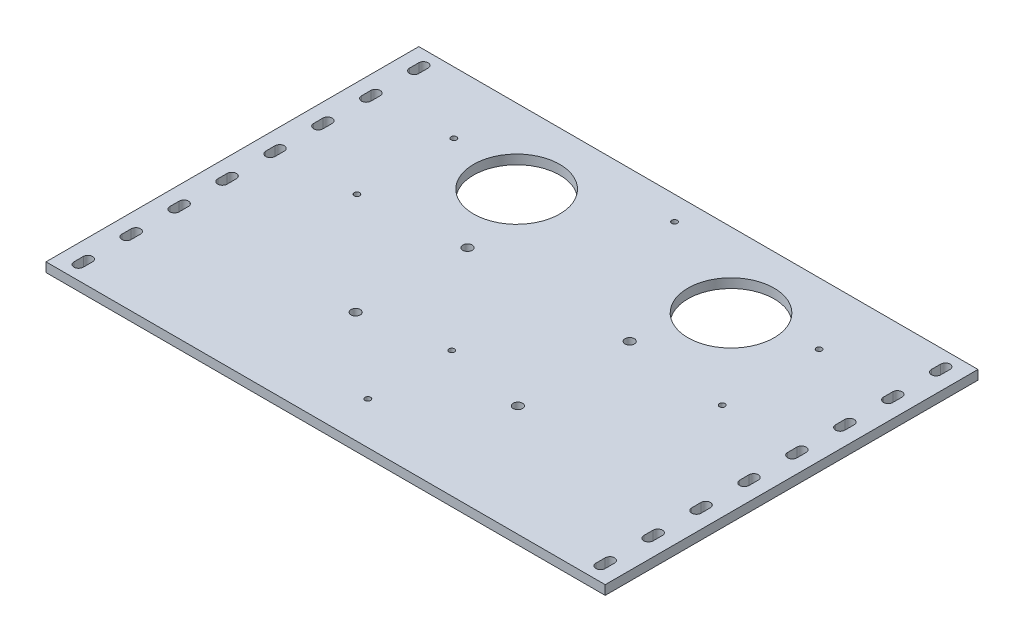
SolidWorks part; units mm, degrees
ref_plane "前基準面" through (0, 0, 0) normal (0, 0, 1) x (1, 0, 0)
ref_plane "上基準面" through (0, 0, 0) normal (0, 1, 0) x (1, 0, 0)
ref_plane "右基準面" through (0, 0, 0) normal (1, 0, 0) x (0, 0, -1)
sketch "草圖1" plane through (0, 0, 0) normal (0, 1, 0) x (1, 0, 0)
  line L0 (-130, 97.2315) -> (-150, 97.2315) construction
  line L1 (-150, 100) -> (150, 100)
  line L2 (-150, 100) -> (-150, -100)
  line L3 (-150, -100) -> (150, -100)
  line L4 (150, 100) -> (150, -100)
  line L5 (0, 100) -> (0, -100) construction
  line L6 (-150, 0) -> (150, 0) construction
  line L7 (-150, 100) -> (-130, 100) construction
  line L8 (150, -90) -> (-150, -90) construction
  line L9 (-150, 100) -> (-150, -100) construction
  line L10 (-150, -100) -> (-130, -100) construction
  line L11 (-130, 100) -> (-130, -100) construction
  line L12 (-142.25, 100) -> (-137.75, 100) construction
  line L13 (-142.25, 100) -> (-142.25, -100) construction
  line L14 (-142.25, -100) -> (-137.75, -100) construction
  line L15 (-137.75, 100) -> (-137.75, -100) construction
  line L16 (-140, 99.6012) -> (-140, 93.2772) construction
  line L17 (-140, 92.5) -> (-140, 87.5) construction
  line L18 (-137.5, 92.5) -> (-137.5, 87.5)
  line L19 (-142.5, 92.5) -> (-142.5, 87.5)
  line L20 (-140, 66.7857) -> (-140, 61.7857) construction
  line L21 (-137.5, 66.7857) -> (-137.5, 61.7857)
  line L22 (-142.5, 66.7857) -> (-142.5, 61.7857)
  line L23 (-140, 41.0714) -> (-140, 36.0714) construction
  line L24 (-137.5, 41.0714) -> (-137.5, 36.0714)
  line L25 (-142.5, 41.0714) -> (-142.5, 36.0714)
  line L26 (-140, 15.3571) -> (-140, 10.3571) construction
  line L27 (-137.5, 15.3571) -> (-137.5, 10.3571)
  line L28 (-142.5, 15.3571) -> (-142.5, 10.3571)
  line L29 (-140, -10.3571) -> (-140, -15.3571) construction
  line L30 (-137.5, -10.3571) -> (-137.5, -15.3571)
  line L31 (-142.5, -10.3571) -> (-142.5, -15.3571)
  line L32 (-140, -36.0714) -> (-140, -41.0714) construction
  line L33 (-137.5, -36.0714) -> (-137.5, -41.0714)
  line L34 (-142.5, -36.0714) -> (-142.5, -41.0714)
  line L35 (-140, -61.7857) -> (-140, -66.7857) construction
  line L36 (-137.5, -61.7857) -> (-137.5, -66.7857)
  line L37 (-142.5, -61.7857) -> (-142.5, -66.7857)
  line L38 (-140, -87.5) -> (-140, -92.5) construction
  line L39 (-137.5, -87.5) -> (-137.5, -92.5)
  line L40 (-142.5, -87.5) -> (-142.5, -92.5)
  line L41 (140, 92.5) -> (140, 87.5) construction
  line L44 (137.5, 92.5) -> (137.5, 87.5)
  line L47 (142.5, 92.5) -> (142.5, 87.5)
  line L50 (140, 66.7857) -> (140, 61.7857) construction
  line L53 (137.5, 66.7857) -> (137.5, 61.7857)
  line L56 (142.5, 66.7857) -> (142.5, 61.7857)
  line L59 (140, 41.0714) -> (140, 36.0714) construction
  line L62 (137.5, 41.0714) -> (137.5, 36.0714)
  line L65 (-150, -100) -> (150, -100) construction
  line L66 (-150, -100) -> (-150, -80) construction
  line L67 (-150, -80) -> (150, -80) construction
  line L68 (150, -100) -> (150, -80) construction
  line L69 (109.7962, -80) -> (109.7962, -100) construction
  line L76 (142.5, 41.0714) -> (142.5, 36.0714)
  line L77 (140, 15.3571) -> (140, 10.3571) construction
  line L78 (137.5, 15.3571) -> (137.5, 10.3571)
  line L79 (142.5, 15.3571) -> (142.5, 10.3571)
  line L80 (140, -10.3571) -> (140, -15.3571) construction
  line L81 (137.5, -10.3571) -> (137.5, -15.3571)
  line L82 (142.5, -10.3571) -> (142.5, -15.3571)
  line L83 (140, -36.0714) -> (140, -41.0714) construction
  line L84 (137.5, -36.0714) -> (137.5, -41.0714)
  line L85 (142.5, -36.0714) -> (142.5, -41.0714)
  line L86 (140, -61.7857) -> (140, -66.7857) construction
  line L87 (137.5, -61.7857) -> (137.5, -66.7857)
  line L88 (142.5, -61.7857) -> (142.5, -66.7857)
  line L89 (140, -87.5) -> (140, -92.5) construction
  line L90 (137.5, -87.5) -> (137.5, -92.5)
  line L91 (142.5, -87.5) -> (142.5, -92.5)
  line L92 (134.459, 100) -> (134.459, 80) construction
  line L93 (-150, 100) -> (150, 100) construction
  line L94 (-150, 100) -> (-150, 80) construction
  line L95 (-150, 80) -> (150, 80) construction
  line L96 (150, 100) -> (150, 80) construction
  arc A9 (-137.5, 92.5) -> (-142.5, 92.5) centre (-140, 92.5) ccw
  arc A10 (-142.5, 87.5) -> (-137.5, 87.5) centre (-140, 87.5) ccw
  arc A11 (-137.5, 66.7857) -> (-142.5, 66.7857) centre (-140, 66.7857) ccw
  arc A12 (-142.5, 61.7857) -> (-137.5, 61.7857) centre (-140, 61.7857) ccw
  arc A13 (-137.5, 41.0714) -> (-142.5, 41.0714) centre (-140, 41.0714) ccw
  arc A14 (-142.5, 36.0714) -> (-137.5, 36.0714) centre (-140, 36.0714) ccw
  arc A15 (-137.5, 15.3571) -> (-142.5, 15.3571) centre (-140, 15.3571) ccw
  arc A16 (-142.5, 10.3571) -> (-137.5, 10.3571) centre (-140, 10.3571) ccw
  arc A17 (-137.5, -10.3571) -> (-142.5, -10.3571) centre (-140, -10.3571) ccw
  arc A18 (-142.5, -15.3571) -> (-137.5, -15.3571) centre (-140, -15.3571) ccw
  arc A19 (-137.5, -36.0714) -> (-142.5, -36.0714) centre (-140, -36.0714) ccw
  arc A20 (-142.5, -41.0714) -> (-137.5, -41.0714) centre (-140, -41.0714) ccw
  arc A21 (-137.5, -61.7857) -> (-142.5, -61.7857) centre (-140, -61.7857) ccw
  arc A22 (-142.5, -66.7857) -> (-137.5, -66.7857) centre (-140, -66.7857) ccw
  arc A23 (-137.5, -87.5) -> (-142.5, -87.5) centre (-140, -87.5) ccw
  arc A24 (-142.5, -92.5) -> (-137.5, -92.5) centre (-140, -92.5) ccw
  arc A45 (137.5, 92.5) -> (142.5, 92.5) centre (140, 92.5) cw
  arc A46 (142.5, 87.5) -> (137.5, 87.5) centre (140, 87.5) cw
  arc A47 (137.5, 66.7857) -> (142.5, 66.7857) centre (140, 66.7857) cw
  arc A48 (142.5, 61.7857) -> (137.5, 61.7857) centre (140, 61.7857) cw
  arc A49 (137.5, 41.0714) -> (142.5, 41.0714) centre (140, 41.0714) cw
  arc A50 (142.5, 36.0714) -> (137.5, 36.0714) centre (140, 36.0714) cw
  arc A51 (137.5, 15.3571) -> (142.5, 15.3571) centre (140, 15.3571) cw
  arc A52 (142.5, 10.3571) -> (137.5, 10.3571) centre (140, 10.3571) cw
  arc A53 (137.5, -10.3571) -> (142.5, -10.3571) centre (140, -10.3571) cw
  arc A54 (142.5, -15.3571) -> (137.5, -15.3571) centre (140, -15.3571) cw
  arc A55 (137.5, -36.0714) -> (142.5, -36.0714) centre (140, -36.0714) cw
  arc A56 (142.5, -41.0714) -> (137.5, -41.0714) centre (140, -41.0714) cw
  arc A57 (137.5, -61.7857) -> (142.5, -61.7857) centre (140, -61.7857) cw
  arc A58 (142.5, -66.7857) -> (137.5, -66.7857) centre (140, -66.7857) cw
  arc A59 (137.5, -87.5) -> (142.5, -87.5) centre (140, -87.5) cw
  arc A60 (142.5, -92.5) -> (137.5, -92.5) centre (140, -92.5) cw
  point P6 (0, 0)
  point P17 (109.7962, -90)
  point P33 (-140, 97.2315)
  point P35 (-140, 90)
  point P42 (-137.5, 90)
  point P43 (-140, 64.2857)
  point P44 (0, 0)
  point P51 (-140, 38.5714)
  point P58 (-140, 12.8571)
  point P65 (-140, -12.8571)
  point P75 (-140, -38.5714)
  point P82 (-140, -64.2857)
  point P89 (-140, -90)
  point P99 (0, 0)
  point P107 (140, 90)
  point P114 (140, 64.2857)
  point P121 (140, 38.5714)
  point P128 (140, 12.8571)
  point P135 (140, -12.8571)
  point P142 (140, -38.5714)
  point P149 (140, -64.2857)
  point P163 (140, -90)
  dimension "D3" = 300
  dimension "D2" = 200
  dimension "D4" = 20
  dimension "D9" = 20
  dimension "D10" = 4.5
  dimension "D11" = 5
  dimension "D12" = 5
  dimension "D13" = 10
  dimension "D15" = 10
  dimension "D16" = 20
  dimension "D17" = 200
  dimension "D14" = 8
extrude "填料-伸長1" add sketch "草圖1" along normal blind 5
sketch "草圖2" plane through (0, 5, 0) normal (0, 1, 0) x (1, 0, 0)
  line L0 (0, 116.4556) -> (0, -113.9778) construction
  line L1 (90, 60) -> (25, 60) construction
  line L2 (-57.5, 92.5) -> (-57.5, 27.5) construction
  line L3 (-90, 60) -> (-25, 60) construction
  line L4 (57.5, 92.5) -> (57.5, 27.5) construction
  line L10 (7.5, -57.8553) -> (-7.5, -57.8553) construction
  line L15 (7.5, -57.8553) -> (7.5, 12.1447) construction
  line L16 (7.5, 12.1447) -> (-7.5, 12.1447) construction
  line L17 (-7.5, -57.8553) -> (-7.5, 12.1447) construction
  line L20 (-7.5, 12.1447) -> (7.5, 12.1447) construction
  line L30 (150, 100) -> (-150, 100) construction
  line L31 (-36, 29.6447) -> (36, 29.6447)
  line L32 (-36, 29.6447) -> (-36, -50.3553)
  line L33 (-36, -50.3553) -> (36, -50.3553)
  line L34 (36, 29.6447) -> (36, -50.3553)
  line L36 (36, -50.3553) -> (-36, -50.3553) construction
  line L37 (36, -50.3553) -> (36, 19.6447) construction
  line L38 (36, 19.6447) -> (-36, 19.6447) construction
  line L39 (-36, -50.3553) -> (-36, 19.6447) construction
  line L52 (144, 10.7857) -> (94, 10.7857)
  line L53 (-144, 70.7857) -> (-94, 70.7857)
  line L54 (-144, 70.7857) -> (-144, 10.7857)
  line L55 (-144, 10.7857) -> (-94, 10.7857)
  line L56 (-94, 70.7857) -> (-94, 10.7857)
  line L57 (94, 70.7857) -> (94, 10.7857)
  line L58 (144, 70.7857) -> (94, 70.7857)
  line L59 (144, 70.7857) -> (144, 10.7857)
  line L60 (-7.5, -10.3553) -> (7.5, -10.3553)
  line L61 (-7.5, -10.3553) -> (-7.5, -35.3553)
  line L62 (-7.5, -35.3553) -> (7.5, -35.3553)
  line L63 (7.5, -10.3553) -> (7.5, -35.3553)
  line L68 (-7.5, -19.8553) -> (7.5, -19.8553) construction
  line L69 (-7.5, -19.8553) -> (-7.5, -89.8553) construction
  line L70 (-7.5, -89.8553) -> (7.5, -89.8553) construction
  line L71 (7.5, -19.8553) -> (7.5, -89.8553) construction
  line L75 (240, -50.3553) -> (-240, -50.3553) construction
  line L76 (240, -50.3553) -> (240, 29.6447) construction
  line L77 (240, 29.6447) -> (-240, 29.6447) construction
  line L78 (-240, -50.3553) -> (-240, 29.6447) construction
  line L79 (35, 29.6447) -> (-35, 29.6447)
  line L80 (35, 29.6447) -> (35, -50.3553)
  line L81 (35, -50.3553) -> (-35, -50.3553)
  line L82 (-35, 29.6447) -> (-35, -50.3553)
  line L83 (0, -50.3553) -> (0, 29.6447) construction
  line L84 (35, -10.3553) -> (-35, -10.3553) construction
  circle A0 centre (-57.5, 60) radius 32.5
  circle A1 centre (-57.5, 60) radius 22.1
  circle A2 centre (-72, 60) radius 2
  circle A3 centre (-43, 60) radius 2
  circle A4 centre (43, 60) radius 2
  circle A5 centre (72, 60) radius 2
  circle A6 centre (57.5, 60) radius 22.1
  circle A7 centre (57.5, 60) radius 32.5
  circle A11 centre (0, -45.3553) radius 1.25 construction
  circle A12 centre (0, 24.6447) radius 35 construction
  circle A13 centre (0, -0.3553) radius 1.25 construction
  circle A24 centre (-140, 66.7857) radius 1.5
  circle A25 centre (-98, 66.7857) radius 1.5
  circle A26 centre (-140, 14.7857) radius 1.5
  circle A27 centre (-98, 14.7857) radius 1.5
  arc A28 (-137.5, 66.7857) -> (-142.5, 66.7857) centre (-140, 66.7857) ccw construction
  circle A29 centre (140, 14.7857) radius 1.5
  circle A30 centre (140, 66.7857) radius 1.5
  circle A34 centre (0, -32.3553) radius 1.5
  circle A35 centre (0, -77.3553) radius 1.5
  point P15 (0, -10.3553)
  point P29 (0, 0)
  point P43 (0, 29.6447)
  point P46 (-7.5, -22.8553)
  point P57 (-7.5, -22.8553)
  point P85 (-96.5, 66.7857)
  point P90 (-141.5, 66.7857)
  point P91 (-140, 13.2857)
  point P92 (-140, 68.2857)
  point P101 (98, 14.7857)
  point P116 (0, -57.8553)
  point P130 (0, -89.8553)
  point P142 (0, -50.3553)
  point P143 (0, -10.3553)
  dimension "D1" = 65
  dimension "D2" = 44.2
  dimension "D4" = 4
  dimension "D8" = 40
  dimension "D10" = 40
  dimension "D7" = 2
  dimension "D16" = 70
  dimension "D13" = 2.5
  dimension "D22" = 60
  dimension "D24" = 45
  dimension "D25" = 3
  dimension "D36" = 45
  dimension "D39" = 3
  dimension "D3" = 29
  dimension "D5" = 50
  dimension "D6" = 12.5
  dimension "D9" = 25
  dimension "D11" = 70
  dimension "D12" = 70
  dimension "D14" = 80
  dimension "D15" = 72
  dimension "D20" = 45
  dimension "D23" = 50
  dimension "D26" = 4
  dimension "D27" = 4
  dimension "D28" = 2
  dimension "D29" = 55
  dimension "D31" = 15
  dimension "D34" = 70
  dimension "D35" = 15
  dimension "D37" = 12.5
  dimension "D38" = 32
  dimension "D43" = 80
  dimension "D44" = 480
  dimension "D45" = 70
sketch "草圖3" plane through (0, 5, 0) normal (0, 1, 0) x (1, 0, 0)
  line L0 (0, 200116.4556) -> (0, -200113.9778) construction
  line L1 (0, 200116.4556) -> (0, -200113.9778) construction
  line L2 (-36, 29.6447) -> (36, 29.6447) construction
  line L3 (-36, 29.6447) -> (-51, 29.6447) construction
  line L4 (-36, 29.6447) -> (-36, 9.6447) construction
  line L5 (-36, 9.6447) -> (-51, 9.6447) construction
  line L6 (-51, 29.6447) -> (-51, 9.6447) construction
  line L7 (0, 0) -> (0, 42.1207) construction
  line L9 (-7.5, -57.8553) -> (-7.5, 12.1447) construction
  line L10 (7.5, 12.1447) -> (-7.5, 12.1447) construction
  line L11 (7.5, 12.1447) -> (7.5, 22.1447) construction
  line L12 (7.5, 22.1447) -> (-7.5, 22.1447) construction
  line L13 (-7.5, 12.1447) -> (-7.5, 22.1447) construction
  circle A0 centre (0, -77.3553) radius 1.5 construction
  circle A1 centre (0, -77.3553) radius 1.5
  circle A2 centre (0, -32.3553) radius 1.5 construction
  circle A3 centre (0, -32.3553) radius 1.5
  circle A4 centre (-98, 14.7857) radius 1.5 construction
  circle A5 centre (-98, 14.7857) radius 1.5
  circle A6 centre (-98, 66.7857) radius 1.5 construction
  circle A7 centre (-98, 66.7857) radius 1.5
  circle A8 centre (98, 14.7857) radius 1.5
  circle A9 centre (98, 66.7857) radius 1.5
  circle A10 centre (-43.5, 19.6447) radius 2.5
  circle A11 centre (43.5, 19.6447) radius 2.5
  circle A12 centre (43.5, -40.3553) radius 2.5
  circle A13 centre (-43.5, -40.3553) radius 2.5
  circle A14 centre (-57.5, 60) radius 22.1 construction
  circle A15 centre (-57.5, 60) radius 22.1 construction
  circle A16 centre (57.5, 60) radius 22.1 construction
  circle A17 centre (57.5, 60) radius 22.1 construction
  circle A18 centre (-57.5, 60) radius 23.1
  circle A19 centre (57.5, 60) radius 23.1
  circle A20 centre (0, 87.1447) radius 1.5
  circle A21 centre (0, 17.1447) radius 2 construction
  point P29 (-51, 19.6447)
  point P32 (-43.5, 9.6447)
  point P61 (0, 17.3646)
  point P62 (-7.5, 17.1447)
  dimension "D2" = 5
  dimension "D8" = 3
  dimension "D11" = 4
  dimension "D1" = 45
  dimension "D3" = 15
  dimension "D4" = 20
  dimension "D5" = 2
  dimension "D6" = 60
  dimension "D9" = 70
  dimension "D10" = 10
  dimension "D7" = 1
extrude "除料-伸長1" cut sketch "草圖3" against normal through all
